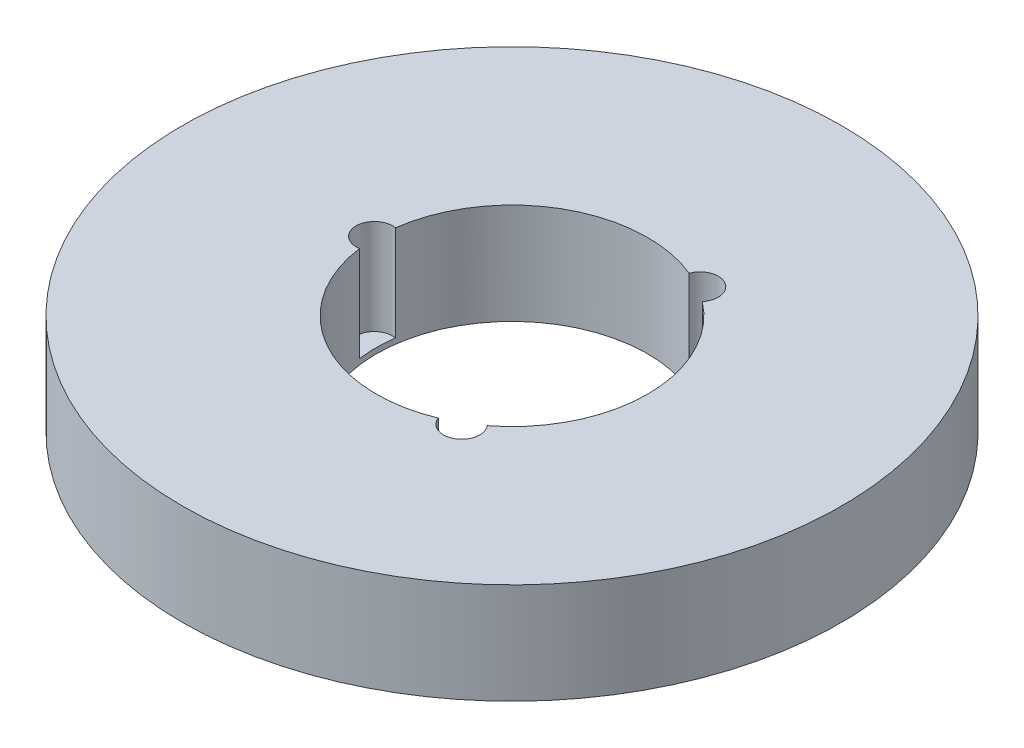
SolidWorks part; units mm, degrees
ref_plane "Front Plane" through (0, 0, 0) normal (0, 0, 1) x (1, 0, 0)
ref_plane "Top Plane" through (0, 0, 0) normal (0, 1, 0) x (1, 0, 0)
ref_plane "Right Plane" through (0, 0, 0) normal (1, 0, 0) x (0, 0, -1)
sketch "Sketch1" plane through (0, 0, 0) normal (0, 1, 0) x (1, 0, 0)
  circle A0 centre (0, 0) radius 85
  dimension "FLANGE_OD" = 170
extrude "Boss-Extrude1" add sketch "Sketch1" along normal blind 26
sketch "Sketch2" plane through (0, 0, 0) normal (0, 1, 0) x (1, 0, 0)
  circle A0 centre (0, 0) radius 35
  dimension "BORE_D" = 70
extrude "Cut-Extrude1" cut sketch "Sketch2" along normal through all
sketch "Sketch3" plane through (0, 26, 0) normal (0, 1, 0) x (1, 0, 0)
  circle A0 centre (0, 0) radius 35.5075 construction
  circle A1 centre (-35.5075, 0) radius 4.6968
  dimension "BOLT_D" = 9.3937
  dimension "BOLT_PCD" = 71.015
extrude "Cut-Extrude2" cut sketch "Sketch3" against normal blind 24.5901
pattern_circular "CirPattern1" count 3 over 360 about axis through (0, 0, 0) along (0, 1, 0) of "Cut-Extrude2"
